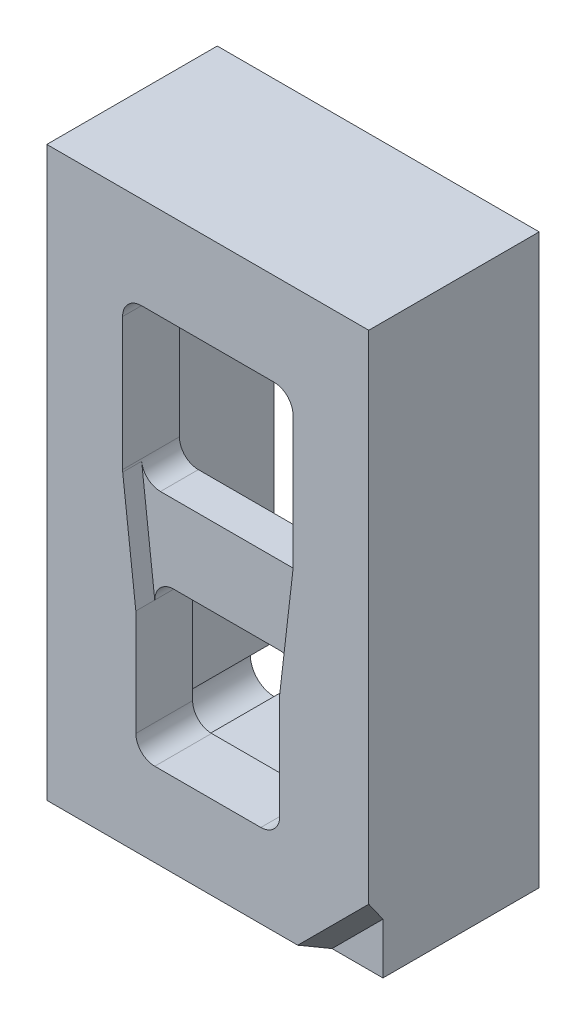
SolidWorks part; units mm, degrees
ref_plane "Front Plane" through (0, 0, 0) normal (0, 0, 1) x (1, 0, 0)
ref_plane "Top Plane" through (0, 0, 0) normal (0, 1, 0) x (1, 0, 0)
ref_plane "Right Plane" through (0, 0, 0) normal (1, 0, 0) x (0, 0, -1)
sketch "Sketch1" plane through (0, 0, 0) normal (0, 0, 1) x (1, 0, 0)
  line L0 (0, 0) -> (0, 1.125) construction
  line L1 (1.1, -2.4) -> (-1.1, -2.4)
  line L2 (1.1, -2.4) -> (1.1, 2.4)
  line L3 (1.1, 2.4) -> (-1.1, 2.4)
  line L4 (-1.1, -2.4) -> (-1.1, 2.4)
  line L5 (1.1, -2.4) -> (-1.1, 2.4) construction
  line L6 (1.1, 2.4) -> (-1.1, -2.4) construction
  line L7 (0, 0) -> (0, -1.258) construction
  line L8 (0, -1.258) -> (0, -1.358) construction
  line L9 (-0.9, 0.225) -> (0.9, 0.225)
  line L10 (-0.9, 0.225) -> (-0.9, 2.025)
  line L11 (-0.9, 2.025) -> (0.9, 2.025)
  line L12 (0.9, 0.225) -> (0.9, 2.025)
  line L13 (-0.9, 0.225) -> (0.9, 2.025) construction
  line L14 (-0.9, 2.025) -> (0.9, 0.225) construction
  line L15 (-0.76, -0.598) -> (0.76, -0.598)
  line L16 (-0.76, -0.598) -> (-0.76, -2.118)
  line L17 (-0.76, -2.118) -> (0.76, -2.118)
  line L18 (0.76, -0.598) -> (0.76, -2.118)
  line L19 (-0.76, -0.598) -> (0.76, -2.118) construction
  line L20 (-0.76, -2.118) -> (0.76, -0.598) construction
  point P0 (0, 0)
  dimension "D4" = 1.8
  dimension "D5" = 1.52
  dimension "D1" = 2.2
  dimension "D2" = 4.8
  dimension "D3" = 1.125
  dimension "D6" = 1.258
  dimension "D7" = 0.1
extrude "Boss-Extrude1" add sketch "Sketch1" along normal blind 0.6
sketch "Sketch2" plane through (0, 0, 0) normal (0, 0, 1) x (1, 0, 0)
  line L0 (1.7, 3) -> (-1.7, 3)
  line L1 (-1.7, 3) -> (-1.7, -3)
  line L2 (-1.7, -3) -> (1.7, -3)
  line L3 (1.7, -3) -> (1.7, 3)
  line L4 (-1.1, 2.4) -> (-1.1, -2.4)
  line L5 (-1.1, -2.4) -> (1.1, -2.4)
  line L6 (1.1, -2.4) -> (1.1, 2.4)
  line L7 (1.1, 2.4) -> (-1.1, 2.4)
  line L8 (-1.1, 2.4) -> (-1.1, -2.4)
  line L9 (-1.1, -2.4) -> (1.1, -2.4)
  line L10 (1.1, -2.4) -> (1.1, 2.4)
  line L11 (1.1, 2.4) -> (-1.1, 2.4)
  dimension "D1" = 0
  dimension "D2" = 0.6
extrude "Boss-Extrude2" add sketch "Sketch2" against normal blind 1.2
sketch "Sketch3" plane through (0, 0, 0) normal (0, 0, 1) x (1, 0, 0)
  line L4 (1.7, -3) -> (1.7, 3)
  line L5 (1.7, 3) -> (-1.7, 3)
  line L6 (-1.7, 3) -> (-1.7, -3)
  line L7 (-1.7, -3) -> (1.7, -3)
  line L8 (1.7, -3) -> (1.7, 3)
  line L9 (1.7, 3) -> (-1.7, 3)
  line L10 (-1.7, 3) -> (-1.7, -3)
  line L11 (-1.7, -3) -> (1.7, -3)
  line L12 (-1.1, 2.4) -> (-1.1, -2.4)
  line L13 (-1.1, -2.4) -> (1.1, -2.4)
  line L14 (1.1, -2.4) -> (1.1, 2.4)
  line L15 (1.1, 2.4) -> (-1.1, 2.4)
  line L16 (-1.1, 2.4) -> (-1.1, -2.4)
  line L17 (-1.1, -2.4) -> (1.1, -2.4)
  line L18 (1.1, -2.4) -> (1.1, 2.4)
  line L19 (1.1, 2.4) -> (-1.1, 2.4)
  dimension "D1" = 0
  dimension "D2" = 0
extrude "Boss-Extrude3" add sketch "Sketch3" along normal up to surface (0.6 mm away) up to face at (0, 0, 0.6)
sketch "Sketch4" plane through (0, 0, 0.6) normal (0, 0, 1) x (1, 0, 0)
  line L1 (1.7, -3) -> (0.95, -3)
  line L3 (-1.7, -3) -> (1.7, -3) construction
  line L8 (0.95, -3) -> (1.7, -2.25)
  line L9 (1.7, -3) -> (1.7, 3) construction
  line L10 (1.7, -2.25) -> (1.7, -3)
  dimension "D1" = 0.75
extrude "Cut-Extrude1" cut sketch "Sketch4" against normal blind 0.15
fillet "Fillet1" radius 0.2 8 edges at (0.9, 0.225, 0.3) (0.76, -2.118, 0.3) (-0.9, 0.225, 0.3) (-0.76, -2.118, 0.3) (0.76, -0.598, 0.3) (0.9, 2.025, 0.3) (-0.76, -0.598, 0.3) (-0.9, 2.025, 0.3)
draft "Draft1" type of draft neutral plane draft angle 45 faces to draft 1 face at (1.325, -2.625, 0.525) neutral plane through (0, 0, 0.6) neutral plane normal (0, 0, 1) parameters "D1"=45
sketch "Sketch5" plane through (0, 0, 0.6) normal (0, 0, 1) x (1, 0, 0)
  line L0 (-0.8987, 0.402) -> (-0.76, -0.798)
  line L1 (0.76, -0.798) -> (0.8987, 0.402)
  line L2 (-0.8987, 0.402) -> (0.8987, 0.402)
  line L3 (-0.76, -0.798) -> (0.76, -0.798)
  arc A1 (0.7, 0.225) -> (0.9, 0.425) centre (0.7, 0.425) ccw construction
  arc A2 (-0.9, 0.425) -> (-0.7, 0.225) centre (-0.7, 0.425) ccw construction
extrude "Cut-Extrude2" cut sketch "Sketch5" against normal blind 0.2
sketch "Sketch6" [suppressed] plane through (0, 0, 1.2) normal (0, 0, 1) x (1, 0, 0)
  line L1 (0.76, -0.798) -> (0.8987, 0.402) construction
  line L2 (-0.8987, 0.402) -> (-0.76, -0.798) construction
  line L3 (0.76, -0.798) -> (0.8987, 0.402)
  line L4 (-0.8987, 0.402) -> (-0.76, -0.798)
  line L5 (-0.76, -0.798) -> (0.76, -0.798)
  line L6 (-0.8987, 0.402) -> (0.8987, 0.402)
extrude "Boss-Extrude4" [suppressed] add sketch "Sketch6" along normal blind 0.4 separate body
sketch "Sketch7" [suppressed] plane through (0, 0, 1.2) normal (0, 0, 1) x (1, 0, 0)
  line L0 (-0.9, 1.825) -> (-0.9, 0.425) construction
  line L1 (-0.9, 1.825) -> (-0.9, 0.425)
  line L2 (-0.56, -2.118) -> (0.56, -2.118) construction
  line L3 (-0.76, -0.798) -> (-0.76, -1.918) construction
  line L4 (-0.8987, 0.402) -> (-0.76, -0.798) construction
  line L5 (0.76, -1.918) -> (0.76, -0.798) construction
  line L6 (0.76, -0.798) -> (0.8987, 0.402) construction
  line L7 (0.9, 0.425) -> (0.9, 1.825) construction
  line L8 (0.7, 2.025) -> (-0.7, 2.025) construction
  line L9 (-0.56, -2.118) -> (0.56, -2.118)
  line L10 (-0.76, -0.798) -> (-0.76, -1.918)
  line L11 (-0.8987, 0.402) -> (-0.76, -0.798)
  line L12 (0.76, -1.918) -> (0.76, -0.798)
  line L13 (0.76, -0.798) -> (0.8987, 0.402)
  line L14 (0.9, 0.425) -> (0.9, 1.825)
  line L15 (0.7, 2.025) -> (-0.7, 2.025)
  arc A0 (-0.9, 0.425) -> (-0.8987, 0.402) centre (-0.7, 0.425) ccw construction
  arc A1 (0.56, -2.118) -> (0.76, -1.918) centre (0.56, -1.918) ccw construction
  arc A2 (-0.76, -1.918) -> (-0.56, -2.118) centre (-0.56, -1.918) ccw construction
  arc A3 (0.8987, 0.402) -> (0.9, 0.425) centre (0.7, 0.425) ccw construction
  arc A4 (0.9, 1.825) -> (0.7, 2.025) centre (0.7, 1.825) ccw construction
  arc A5 (-0.7, 2.025) -> (-0.9, 1.825) centre (-0.7, 1.825) ccw construction
  arc A6 (-0.9, 0.425) -> (-0.8987, 0.402) centre (-0.7, 0.425) ccw
  arc A7 (0.56, -2.118) -> (0.76, -1.918) centre (0.56, -1.918) ccw
  arc A8 (-0.76, -1.918) -> (-0.56, -2.118) centre (-0.56, -1.918) ccw
  arc A9 (0.8987, 0.402) -> (0.9, 0.425) centre (0.7, 0.425) ccw
  arc A10 (0.9, 1.825) -> (0.7, 2.025) centre (0.7, 1.825) ccw
  arc A11 (-0.7, 2.025) -> (-0.9, 1.825) centre (-0.7, 1.825) ccw
extrude "Boss-Extrude5" [suppressed] add sketch "Sketch7" along normal blind 0.4 draft 45 separate body draft outward yes
sketch "Sketch9" plane through (0, 0, -1.2) normal (0, 0, -1) x (-1, 0, 0)
  circle A0 centre (1.1, 2.4) radius 0.25
  circle A1 centre (-1.1, 2.4) radius 0.25
  circle A2 centre (1.1, -2.4) radius 0.25
  circle A3 centre (-1.1, -2.4) radius 0.25
  dimension "D1" = 0.5
extrude "Cut-Extrude4" cut sketch "Sketch9" against normal up to surface (1.2 mm away) up to face at (0, -1.358, 0)
